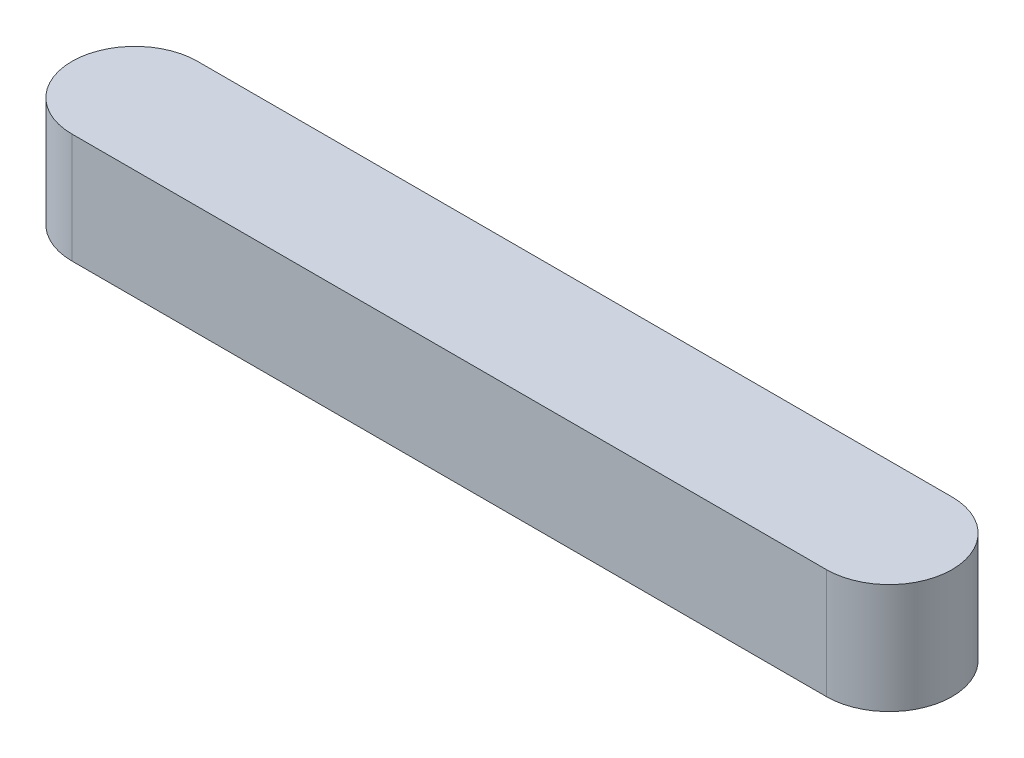
SolidWorks part; units mm, degrees
ref_plane "Спереди" through (0, 0, 0) normal (0, 0, 1) x (1, 0, 0)
ref_plane "Сверху" through (0, 0, 0) normal (0, 1, 0) x (1, 0, 0)
ref_plane "Справа" through (0, 0, 0) normal (1, 0, 0) x (0, 0, -1)
sketch "Эскиз1" plane through (0, 0, 0) normal (0, 1, 0) x (1, 0, 0)
  line L0 (0, 0) -> (48, 0) construction
  line L2 (0, 4) -> (48, 4)
  line L3 (0, -4) -> (48, -4)
  arc A0 (0, 4) -> (0, -4) centre (0, 0) ccw
  arc A1 (48, -4) -> (48, 4) centre (48, 0) ccw
  point P5 (24, 0)
extrude "Бобышка-Вытянуть1" add sketch "Эскиз1" along normal blind 7
